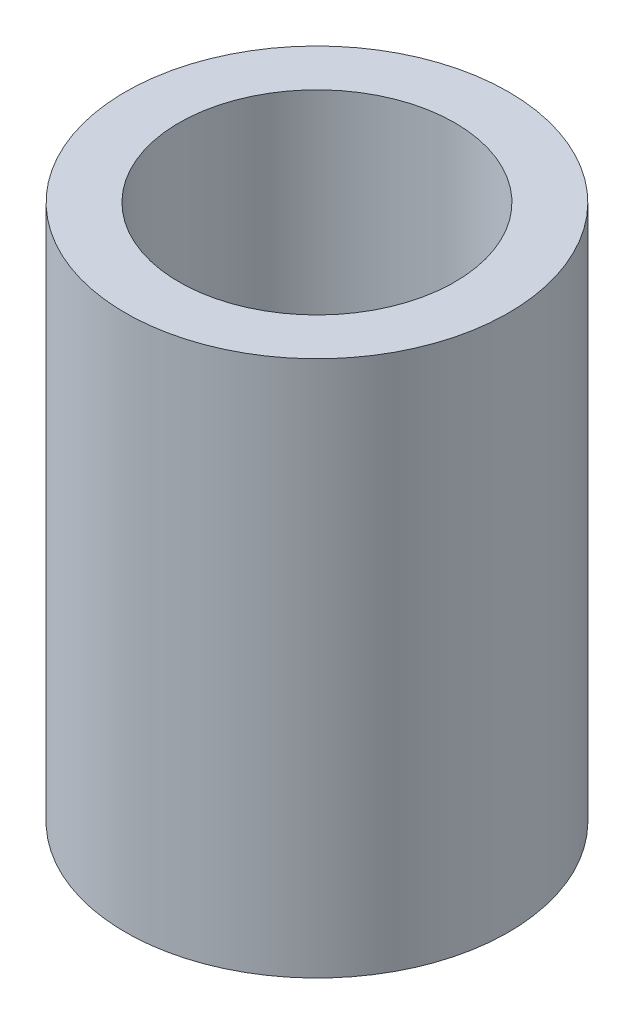
SolidWorks part; units mm, degrees
ref_plane "Front Plane" through (0, 0, 0) normal (0, 0, 1) x (1, 0, 0)
ref_plane "Top Plane" through (0, 0, 0) normal (0, 1, 0) x (1, 0, 0)
ref_plane "Right Plane" through (0, 0, 0) normal (1, 0, 0) x (0, 0, -1)
sketch "Sketch1" plane through (0, 0, 0) normal (0, 0, 1) x (1, 0, 0)
  line L0 (0, 0) -> (0, 36.1586) construction
  line L1 (12.5, 0) -> (12.5, 35)
  line L2 (12.5, 35) -> (9, 35)
  line L3 (9, 35) -> (9, 11)
  line L6 (9, 11) -> (11, 11)
  line L7 (11, 11) -> (11, 0)
  line L8 (11, 0) -> (12.5, 0)
  point P8 (8.7264, 1.083)
  point P11 (9.5098, 23.1067)
  point P12 (6.6102, 23.1734)
  point P13 (8.9461, 22.7694)
  dimension "D1" = 25
  dimension "D2" = 22
  dimension "D3" = 18
  dimension "D4" = 24
  dimension "D5" = 35
revolve "Revolve1" add sketch "Sketch1" angle 360 about L0
